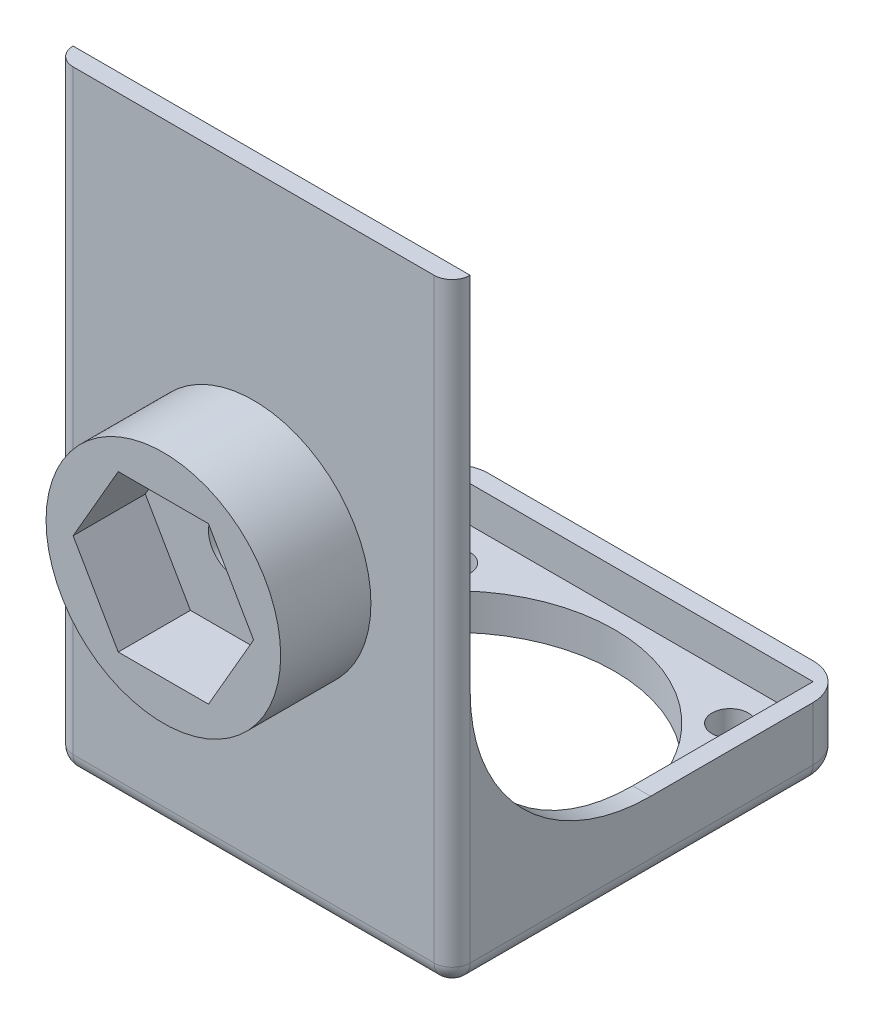
SolidWorks part; units mm, degrees
material "5052-H32"
ref_plane "前视基准面" through (0, 0, 0) normal (0, 0, 1) x (1, 0, 0)
ref_plane "上视基准面" through (0, 0, 0) normal (0, 1, 0) x (1, 0, 0)
ref_plane "右视基准面" through (0, 0, 0) normal (1, 0, 0) x (0, 0, -1)
sketch "草图1" plane through (0, 0, 0) normal (0, 1, 0) x (1, 0, 0)
  line L1 (0, 0) -> (20, 0)
  line L2 (0, 0) -> (0, 20)
  line L3 (0, 20) -> (20, 20)
  line L4 (20, 0) -> (20, 20)
  line L7 (-1, -1) -> (21, -1)
  line L8 (-1, -1) -> (-1, 21)
  line L9 (-1, 21) -> (21, 21)
  line L10 (21, -1) -> (21, 21)
extrude "凸台-拉伸1" add sketch "草图1" along normal blind 4
sketch "草图2" plane through (0, 0, 0) normal (0, 1, 0) x (1, 0, 0)
  line L0 (0, 0) -> (20, 0) construction
  line L1 (0, 20) -> (20, 20)
  line L2 (0, 20) -> (0, 0)
  line L3 (0, 0) -> (20, 0)
  line L4 (20, 20) -> (20, 0)
  line L5 (20, 0) -> (20, 20) construction
extrude "凸台-拉伸2" add sketch "草图2" along normal blind 2 contours L2 L1 L4 L3
sketch "草图3" plane through (0, 2, 0) normal (0, 1, 0) x (1, 0, 0)
  line L0 (0, 10) -> (20, 10)
  line L1 (0, 20) -> (0, 0) construction
  line L2 (20, 0) -> (20, 20) construction
  circle A0 centre (10, 10) radius 9
extrude "切除-拉伸1" cut sketch "草图3" against normal blind 2 contours L0 A0 | L0 A0 region at (10, 2, -13.8197) region at (10, 2, -6.1803)
sketch "草图4" plane through (0, 2, 0) normal (0, 1, 0) x (1, 0, 0)
  circle A0 centre (2.3, 17.7) radius 1
  circle A1 centre (17.7, 17.7) radius 1
  circle A2 centre (17.7, 2.3) radius 1
  circle A3 centre (2.3, 2.3) radius 1
extrude "切除-拉伸2" cut sketch "草图4" against normal blind 2
sketch "草图5" plane through (0, 4, 0) normal (0, 1, 0) x (1, 0, 0)
  line L0 (0, 0) -> (0, 10)
  line L1 (0, 20) -> (0, 0) construction
  line L2 (0, 10) -> (-1, 10)
  line L3 (-1, 21) -> (-1, -1) construction
  line L4 (-1, 10) -> (-1, -1)
  line L5 (-1, -1) -> (21, -1)
  line L6 (21, -1) -> (21, 10)
  line L7 (21, -1) -> (21, 21) construction
  line L8 (21, 10) -> (20, 10)
  line L9 (20, 20) -> (20, 0) construction
  line L10 (20, 10) -> (20, 0)
  line L11 (20, 0) -> (0, 0)
extrude "凸台-拉伸4" add sketch "草图5" along normal blind 30
sketch "草图7" plane through (-1, 0, 0) normal (-1, 0, 0) x (0, 0, 1)
  line L0 (1, 34) -> (0, 34)
  line L1 (-10, 34) -> (1, 34) construction
  line L2 (0, 34) -> (0, 4)
  line L3 (0, 4) -> (-10, 4)
  line L4 (-10, 4) -> (-10, 14)
  line L5 (-10, 34) -> (-10, 4) construction
  line L6 (-10, 14) -> (0, 14)
  line L7 (0, 14) -> (0, 34)
  line L8 (-10, 34) -> (0, 34)
  line L9 (-10, 34) -> (-10, 14)
  circle A0 centre (-10, 14) radius 10
  line M10 (1, 34) -> (-10, 34)
  line M11 (-10, 34) -> (-10, 4)
extrude "切除-拉伸3" cut sketch "草图7" against normal through all contours A0 L6 M11 | L6 A0 L9 | A0 L2 M10 M11 region at (-1, 27.7219, -4.5112) region at (-1, 9.7559, -5.7559) region at (-1, 18.2441, -5.7559)
sketch "草图8" plane through (0, 0, 0) normal (0, 0, -1) x (-1, 0, 0)
  line L1 (-21, 4) -> (1, 4) construction
  line L4 (1, 4) -> (-10, 4)
  line L5 (-10, 4) -> (-10, 16.5)
  circle A0 centre (-10, 16.5) radius 2.5
extrude "切除-拉伸4" cut sketch "草图8" against normal blind 4 contours A0
sketch "草图10" plane through (0, 0, 1) normal (0, 0, 1) x (1, 0, 0)
  circle A0 centre (10, 16.5) radius 6.5
extrude "凸台-拉伸5" add sketch "草图10" along normal blind 5
sketch "草图11" plane through (0, 0, 6) normal (0, 0, 1) x (1, 0, 0)
  line L1 (15, 16.5) -> (12.5, 20.8301)
  line L2 (12.5, 20.8301) -> (7.5, 20.8301)
  line L3 (7.5, 20.8301) -> (5, 16.5)
  line L4 (5, 16.5) -> (7.5, 12.1699)
  line L5 (7.5, 12.1699) -> (12.5, 12.1699)
  line L6 (12.5, 12.1699) -> (15, 16.5)
  circle A1 centre (10, 16.5) radius 4.3301 construction
extrude "切除-拉伸5" cut sketch "草图11" against normal blind 4
sketch "草图12" plane through (0, 0, 1) normal (0, 0, -1) x (-1, 0, 0)
  circle A0 centre (-10, 16.5) radius 1.5
extrude "切除-拉伸6" cut sketch "草图12" against normal blind 4
fillet "圆角2" radius 2 1 edges at (-1, 2, -21)
fillet "圆角3" radius 2 1 edges at (21, 2, -21)
fillet "圆角4" radius 1 1 edges at (21, 17, 1)
fillet "圆角5" radius 1 1 edges at (-1, 17, 1)
fillet "圆角6" radius 1 8 edges at (-0.4142, 0, -20.4142) (10, 0, -21) (20.4142, 0, -20.4142) (21, 0, -9.5) (20.7071, 0, 0.7071) (10, 0, 1) (-0.7071, 0, 0.7071) (-1, 0, -9.5)
